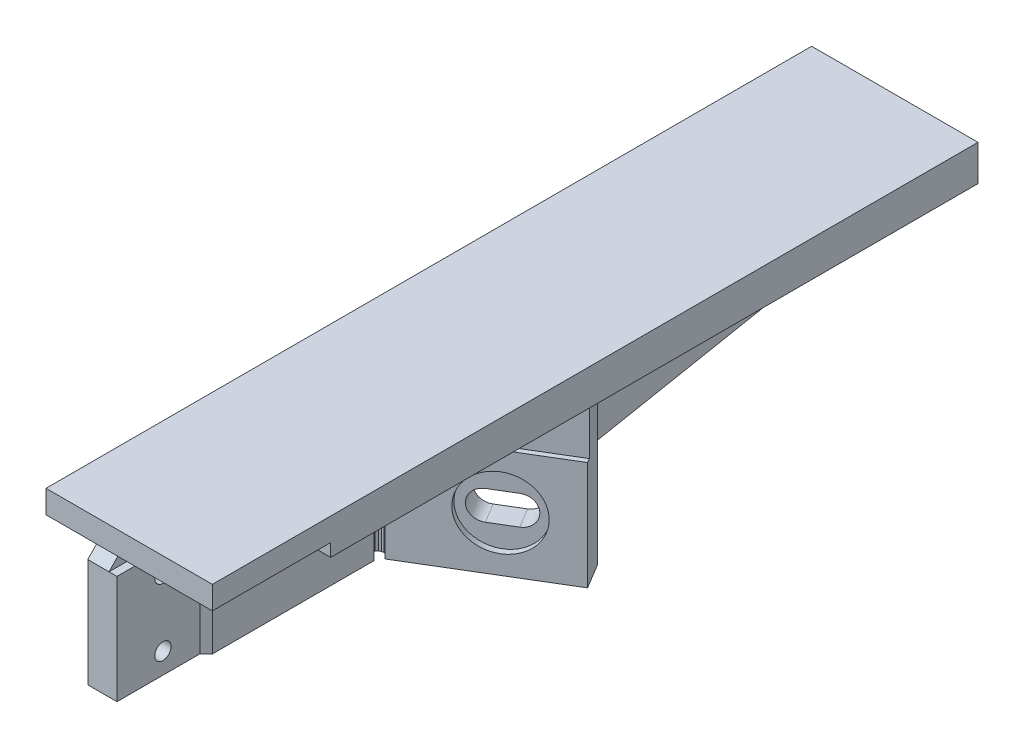
SolidWorks part; units mm, degrees
ref_plane "Front Plane" through (0, 0, 0) normal (0, 0, 1) x (1, 0, 0)
ref_plane "Top Plane" through (0, 0, 0) normal (0, 1, 0) x (1, 0, 0)
ref_plane "Right Plane" through (0, 0, 0) normal (1, 0, 0) x (0, 0, -1)
ref_plane "PY -20.700" through (0, -20.7, 0) normal (0, 1, 0) x (1, 0, 0)
sketch "leg and pad sketch" plane through (0, -20.7, 0) normal (0, 1, 0) x (1, 0, 0)
  line L0 (0.5513, 30.3327) -> (0.3673, 30.8194)
  line L1 (0.3673, 30.8194) -> (0.028, 31.2139)
  line L2 (0.028, 31.2139) -> (-0.4256, 31.4688)
  line L3 (-0.4256, 31.4688) -> (-0.939, 31.5534)
  line L4 (-0.939, 31.5534) -> (-1.4504, 31.4576)
  line L5 (-1.4504, 31.4576) -> (-1.8983, 31.1928)
  line L6 (-1.8983, 31.1928) -> (-2.2288, 30.7909)
  line L7 (-2.2288, 30.7909) -> (-2.4021, 30.3003)
  line L8 (-2.4021, 30.3003) -> (-2.3973, 29.78)
  line L9 (-2.3973, 29.78) -> (-2.2152, 29.2926)
  line L10 (-2.2152, 29.2926) -> (-1.8775, 28.8968)
  line L11 (-1.8775, 28.8968) -> (-1.4248, 28.6402)
  line L12 (-1.4248, 28.6402) -> (-0.9118, 28.5536)
  line L13 (-0.9118, 28.5536) -> (-0.4, 28.6475)
  line L14 (-0.4, 28.6475) -> (-0.4, -9.98)
  line L15 (-0.4, -9.98) -> (-1.92, -11.5)
  line L16 (-1.92, -11.5) -> (-1.92, -31.37)
  line L17 (-1.92, -31.37) -> (-8.92, -31.37)
  line L18 (-8.92, -31.37) -> (-8.92, 32.7926)
  line L19 (-8.92, 32.7926) -> (27.2048, 54.5947)
  line L20 (27.2048, 54.5947) -> (30.8218, 48.6015)
  line L21 (30.8218, 48.6015) -> (0.5513, 30.3327)
extrude "leg and pad" add sketch "leg and pad sketch" along normal mid plane 26
ref_plane "PX -1.350" through (-1.35, 0, 0) normal (1, 0, 0) x (0, 0, -1)
sketch "screw head relief sketch" plane through (-1.35, 0, 0) normal (1, 0, 0) x (0, 0, -1)
  line L0 (23.4, -12.7) -> (23.4, -6.7)
  line L1 (23.4, -6.7) -> (9.4, -6.7)
  line L2 (9.4, -6.7) -> (9.4, -12.7)
  line L3 (9.4, -12.7) -> (23.4, -12.7)
extrude "screw head relief" cut sketch "screw head relief sketch" against normal mid plane 4.7
sketch "insert flange relief sketch" plane through (0, -20.7, 0) normal (0, 1, 0) x (1, 0, 0)
  line L0 (18.3249, 39.8914) -> (17.0331, 42.0318)
  line L1 (17.0331, 42.0318) -> (9.7557, 37.6398)
  line L2 (9.7557, 37.6398) -> (11.0475, 35.4994)
  line L3 (11.0475, 35.4994) -> (18.3249, 39.8914)
revolve "insert flange relief" cut sketch "insert flange relief sketch" angle 360 about L0
sketch "M6 slot end 1 sketch" plane through (0, -20.7, 0) normal (0, 1, 0) x (1, 0, 0)
  line L0 (20.8933, 41.4415) -> (16.243, 49.147)
  line L1 (16.243, 49.147) -> (13.2464, 47.3385)
  line L2 (13.2464, 47.3385) -> (17.8968, 39.633)
  line L3 (17.8968, 39.633) -> (20.8933, 41.4415)
revolve "M6 slot end 1" cut sketch "M6 slot end 1 sketch" angle 360 about L0
sketch "M6 slot end 2 sketch" plane through (0, -20.7, 0) normal (0, 1, 0) x (1, 0, 0)
  line L0 (15.7564, 38.3413) -> (11.106, 46.0467)
  line L1 (11.106, 46.0467) -> (8.1094, 44.2382)
  line L2 (8.1094, 44.2382) -> (12.7598, 36.5328)
  line L3 (12.7598, 36.5328) -> (15.7564, 38.3413)
revolve "M6 slot end 2" cut sketch "M6 slot end 2 sketch" angle 360 about L0
sketch "M6 slot middle sketch" plane through (0, -20.7, 0) normal (0, 1, 0) x (1, 0, 0)
  line L0 (15.7564, 38.3413) -> (20.8933, 41.4415)
  line L1 (20.8933, 41.4415) -> (16.243, 49.147)
  line L2 (16.243, 49.147) -> (11.106, 46.0467)
  line L3 (11.106, 46.0467) -> (15.7564, 38.3413)
extrude "M6 slot middle" cut sketch "M6 slot middle sketch" against normal mid plane 7
ref_plane "PX -5.420" through (-5.42, 0, 0) normal (1, 0, 0) x (0, 0, -1)
sketch "screw holes sketch" plane through (-5.42, 0, 0) normal (1, 0, 0) x (0, 0, -1)
  circle A0 centre (-20.375, -28.7) radius 1.95
  circle A1 centre (-20.375, -12.7) radius 1.95
extrude "screw holes" cut sketch "screw holes sketch" against normal mid plane 9
ref_plane "PY -2.100" through (0, -2.1, 0) normal (0, 1, 0) x (1, 0, 0)
sketch "foot leg sketch" plane through (0, -2.1, 0) normal (0, 1, 0) x (1, 0, 0)
  line L0 (-2.3, 30.0135) -> (-2.3, -9.98)
  line L1 (-2.3, -9.98) -> (-8.92, -9.98)
  line L2 (-8.92, -9.98) -> (-8.92, 32.7926)
  line L3 (-8.92, 32.7926) -> (27.2048, 54.5947)
  line L4 (27.2048, 54.5947) -> (30.2017, 49.6289)
  line L5 (30.2017, 49.6289) -> (-2.3, 30.0135)
extrude "foot leg" add sketch "foot leg sketch" along normal mid plane 12.2
ref_plane "PY 7.785" through (0, 7.785, 0) normal (0, 1, 0) x (1, 0, 0)
sketch "sole under the housing sketch" plane through (0, 7.785, 0) normal (0, 1, 0) x (1, 0, 0)
  line L0 (30.9218, 142) -> (-8.92, 142)
  line L1 (-8.92, 142) -> (-8.92, -13.03)
  line L2 (-8.92, -13.03) -> (30.9218, -13.03)
  line L3 (30.9218, -13.03) -> (30.9218, 142)
extrude "sole under the housing" add sketch "sole under the housing sketch" along normal mid plane 8.57
ref_plane "PY 9.320" through (0, 9.32, 0) normal (0, 1, 0) x (1, 0, 0)
sketch "sole under the block sketch" plane through (0, 9.32, 0) normal (0, 1, 0) x (1, 0, 0)
  line L0 (30.9218, -12.53) -> (-8.92, -12.53)
  line L1 (-8.92, -12.53) -> (-8.92, -41.37)
  line L2 (-8.92, -41.37) -> (30.9218, -41.37)
  line L3 (30.9218, -41.37) -> (30.9218, -12.53)
extrude "sole under the block" add sketch "sole under the block sketch" along normal mid plane 5.5
ref_plane "PX -6.370" through (-6.37, 0, 0) normal (1, 0, 0) x (0, 0, -1)
sketch "seat gusset sketch" plane through (-6.37, 0, 0) normal (1, 0, 0) x (0, 0, -1)
  line L0 (-9.48, -8.2) -> (-31.37, -8.2)
  line L1 (-31.37, -8.2) -> (-31.37, -7.7)
  line L2 (-31.37, -7.7) -> (-17.1, 7.07)
  line L3 (-17.1, 7.07) -> (-9.48, 7.07)
  line L4 (-9.48, 7.07) -> (-9.48, -8.2)
extrude "seat gusset" add sketch "seat gusset sketch" along normal mid plane 5.1
ref_plane "PX 19.922" through (19.9218, 0, 0) normal (1, 0, 0) x (0, 0, -1)
sketch "tail rib sketch" plane through (19.9218, 0, 0) normal (1, 0, 0) x (0, 0, -1)
  line L0 (53.1, 4) -> (53.1, -12.5)
  line L1 (53.1, -12.5) -> (57.1, -12.5)
  line L2 (57.1, -12.5) -> (140, 3.5)
  line L3 (140, 3.5) -> (140, 4)
  line L4 (140, 4) -> (53.1, 4)
extrude "tail rib" add sketch "tail rib sketch" along normal mid plane 6
ref_plane "PX -5.210" through (-5.21, 0, 0) normal (1, 0, 0) x (0, 0, -1)
sketch "side brace sketch" plane through (-5.21, 0, 0) normal (1, 0, 0) x (0, 0, -1)
  line L0 (142, 4) -> (142, 0.5)
  line L1 (142, 0.5) -> (37.7926, -33.7)
  line L2 (37.7926, -33.7) -> (31.7926, -33.7)
  line L3 (31.7926, -33.7) -> (31.7926, 4)
  line L4 (31.7926, 4) -> (142, 4)
extrude "side brace" add sketch "side brace sketch" along normal mid plane 7.42
sketch "screw head relief to the end sketch" plane through (-1.35, 0, 0) normal (1, 0, 0) x (0, 0, -1)
  line L0 (23.4, -12.7) -> (23.4, 3.3)
  line L1 (23.4, 3.3) -> (9.4, 3.3)
  line L2 (9.4, 3.3) -> (9.4, -12.7)
  line L3 (9.4, -12.7) -> (23.4, -12.7)
extrude "screw head relief to the end" cut sketch "screw head relief to the end sketch" against normal mid plane 4.7
equation "\"diffL\" = 608.8mm"
equation "\"diffW\" = 329.4mm"
equation "\"diffT\" = 2.9mm"
equation "\"chanSlotW\" = 12.9mm"
equation "\"chanSlotDepth\" = 11.13mm"
equation "\"chanFloor\" = 1.57mm"
equation "\"chanLeg\" = 12.7mm"
equation "\"lightL\" = 604.8mm"
equation "\"lightW\" = 330.2mm"
equation "\"lightH\" = 92mm"
equation "\"lightSideFlat\" = 30mm"
equation "\"lightSlopeLen\" = 38.9mm"
equation "\"lightWingDepth\" = 50.1mm"
equation "\"lightWingFlat\" = 90.2mm"
equation "\"lightChanW\" = 99.6mm"
equation "\"lightChanStand\" = 44.1mm"
equation "\"insFlangeD\" = 12.3mm"
equation "\"insFromEnd\" = 20.7mm"
equation "\"insUpSlope\" = 20.8mm"
equation "\"gaugeH\" = 10mm"
equation "\"gaugeStepLen\" = 14mm"
equation "\"gaugeStepW0\" = 13.1mm"
equation "\"gaugeStepDW\" = 0.2mm"
equation "\"gaugeSteps\" = 5mm"
equation "\"gaugeHandleLen\" = 30mm"
equation "\"gaugeHandleW\" = 24mm"
equation "\"gaugeSlot0\" = 3mm"
equation "\"gaugeSlotD\" = 0.1mm"
equation "\"gaugeSlotDepth\" = 8mm"
equation "\"gap\" = 25.4mm"
equation "\"edgeL\" = 1mm"
equation "\"edgeW\" = 0.75mm"
equation "\"proud\" = 1.5mm"
equation "\"seatClr\" = 0.15mm"
equation "\"tongueClrZ\" = 0.1mm"
equation "\"tongueClrX\" = 0.25mm"
equation "\"tongueLen\" = 30mm"
equation "\"armSide\" = 45mm"
equation "\"armEnd\" = 20mm"
equation "\"cornerCham\" = 3mm"
equation "\"brkW\" = 26mm"
equation "\"brkT\" = 7mm"
equation "\"brkSeatClr\" = 0.3mm"
equation "\"brkScrewSpan\" = 16mm"
equation "\"pilotD\" = 2.7mm"
equation "\"pilotDepth\" = 10mm"
equation "\"screwClrD\" = 3.9mm"
equation "\"jogBelow\" = 4mm"
equation "\"padT\" = 7mm"
equation "\"padLen\" = 36mm"
equation "\"m6Clr\" = 7mm"
equation "\"m6Slot\" = 6mm"
equation "\"flangeRelD\" = 17mm"
equation "\"flangeRelDepth\" = 1.5mm"
equation "\"relLen\" = 5mm"
equation "\"relDepth\" = 3.3mm"
equation "\"knockN\" = 100mm"
equation "\"petgcfE\" = 3000mm"
equation "\"mockExtent\" = 110mm"
equation "\"relZnear\" = 9.4mm"
equation "\"relZfar\" = 23.4mm"
equation "\"headD\" = 8mm"
equation "\"headH\" = 2.5mm"
equation "\"headFromEnd\" = 6.8mm"
equation "\"headBack\" = 16.4mm"
equation "\"sideClr\" = 0.4mm"
equation "\"cornerRelR\" = 1.5mm"
equation "\"cornerRelBack\" = 0.6mm"
equation "\"endHeadH\" = 2.8mm"
equation "\"footClr\" = 1.2mm"
equation "\"footEndClr\" = 3.5mm"
equation "\"footLift\" = 3.5mm"
equation "\"footBlockClr\" = 0.5mm"
equation "\"footBack\" = 30mm"
equation "\"footFwd\" = 25mm"
equation "\"footRibH\" = 16mm"
equation "\"footRibT\" = 6mm"
equation "\"footBraceEnd\" = 3mm"
equation "\"footLoadN\" = 25mm"
